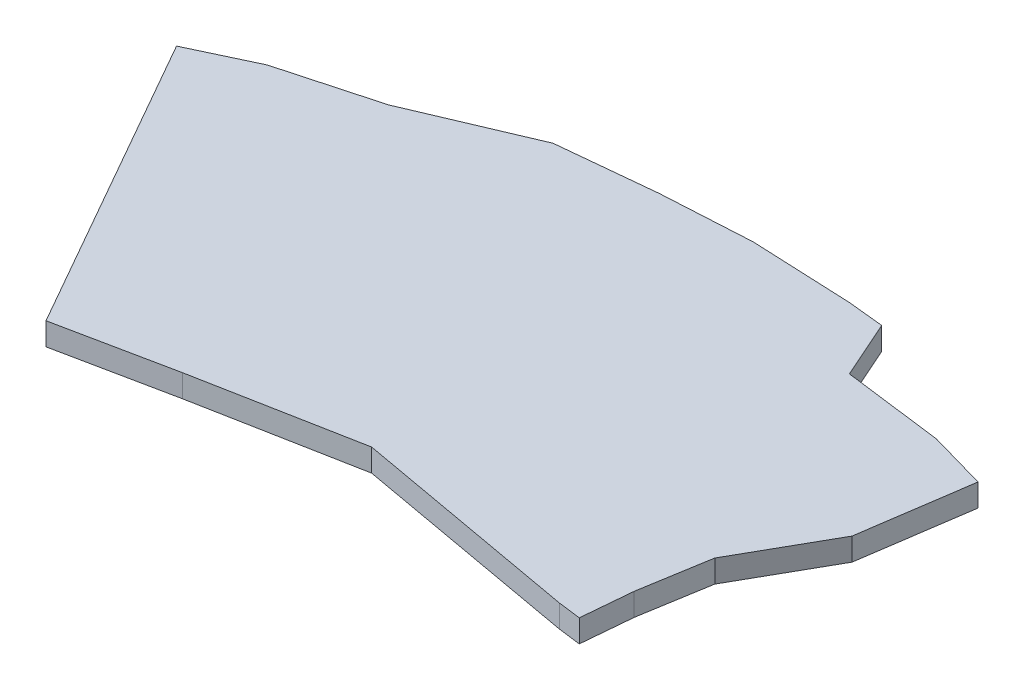
SolidWorks part; units mm, degrees
ref_plane "Спереди" through (0, 0, 0) normal (0, 0, 1) x (1, 0, 0)
ref_plane "Сверху" through (0, 0, 0) normal (0, 1, 0) x (1, 0, 0)
ref_plane "Справа" through (0, 0, 0) normal (1, 0, 0) x (0, 0, -1)
sketch "Sketch1" plane through (0, 0, 0) normal (0, 1, 0) x (1, 0, 0)
  line L0 (-16.2561, 26.609) -> (-10.7964, 29.1722)
  line L4 (-2.3748, 31.4791) -> (7.8402, 35.8163)
  line L8 (16.3824, 36.6681) -> (24.2468, 37.1155)
  line L9 (24.2468, 37.1155) -> (33.2149, 36.7207)
  line L10 (33.2149, 36.7207) -> (36.3351, 36.3935)
  line L11 (36.3351, 36.3935) -> (38.6188, 31.2568)
  line L12 (38.6188, 31.2568) -> (47.4466, 30.1245)
  line L13 (47.4466, 30.1245) -> (52.5867, 28.6628)
  line L14 (52.5867, 28.6628) -> (51.1594, 18.9539)
  line L15 (51.1594, 18.9539) -> (46.7682, 11.1964)
  line L17 (43.3617, 0.8762) -> (23.0896, 4.5213)
  line L18 (23.0896, 4.5213) -> (9.0371, 1.8532)
  line L19 (9.0371, 1.8532) -> (-0.9868, -0.2064)
  line L20 (-0.9868, -0.2064) -> (-16.2561, 26.609)
  line L21 (-10.646, 26.029) -> (-1.0258, 28.7587)
  line L22 (-1.0258, 28.7587) -> (5.2095, 6.7841)
  line L23 (5.2095, 6.7841) -> (-3.5518, 4.2981)
  line L24 (-10.646, 26.029) -> (-5.4017, 7.5469)
  line L25 (7.8554, 33.1374) -> (17.7581, 34.5287)
  line L26 (17.7581, 34.5287) -> (20.9389, 11.8895)
  line L27 (20.9389, 11.8895) -> (11.0362, 10.4981)
  line L28 (11.0362, 10.4981) -> (7.8554, 33.1374)
  line L29 (24.1721, 34.8404) -> (23.1574, 12.3233)
  line L30 (23.1574, 12.3233) -> (33.1473, 11.8731)
  line L31 (33.1473, 11.8731) -> (34.162, 34.3903)
  line L32 (34.162, 34.3903) -> (24.1721, 34.8404)
  line L33 (38.3251, 28.9823) -> (48.1751, 27.2566)
  line L34 (48.1751, 27.2566) -> (44.2664, 4.9462)
  line L35 (44.2664, 4.9462) -> (34.4164, 6.6718)
  line L36 (34.4164, 6.6718) -> (38.3251, 28.9823)
  line L37 (-10.7964, 29.1722) -> (-2.3748, 31.4791)
  line L38 (7.8402, 35.8163) -> (16.3824, 36.6681)
  line L39 (46.7682, 11.1964) -> (45.7548, 5.0853)
  line L40 (45.7548, 5.0853) -> (45.3569, 0.6201)
  line L41 (45.3569, 0.6201) -> (43.3617, 0.8762)
  line L42 (11.3111, 44.4789) -> (16.3337, 8.7301) construction
  line L43 (-8.7492, 37.6606) -> (1.2172, 2.5372) construction
  line L44 (29.2007, 35.3626) -> (28.0257, 9.2891) construction
  line L45 (43.3853, 28.8911) -> (38.8105, 2.7788) construction
  dimension "D1" = 5
  dimension "D2" = 5
  dimension "D3" = 5
  dimension "D4" = 5
  dimension "D5" = 5
  dimension "D6" = 5
  dimension "D7" = 5
  dimension "D8" = 5
extrude "Boss-Extrude1" add sketch "Sketch1" along normal blind 0.1 contours L21 L24 L20 L23 L22 region at (-2.7059, 0, -16.4859)
extrude "Boss-Extrude2" add sketch "Sketch1<4>" against normal blind 0.4 separate body contours L28 L27 L26 L25 region at (14.3972, 0, -22.5134)
sketch "Sketch1<4>" plane through (0, 0, 0) normal (0, 1, 0) x (1, 0, 0) same geometry as "Sketch1"
extrude "Boss-Extrude3" add sketch "Sketch1<6>" against normal blind 1.6 separate body contours L31 L32 L29 L30 region at (28.6597, 0, -23.3568)
sketch "Sketch1<6>" plane through (0, 0, 0) normal (0, 1, 0) x (1, 0, 0) same geometry as "Sketch1"
extrude "Boss-Extrude4" add sketch "Sketch1<7>" against normal blind 1 separate body contours L36 L35 L34 L33 region at (41.2957, 0, -16.9642)
sketch "Sketch1<7>" plane through (0, 0, 0) normal (0, 1, 0) x (1, 0, 0) same geometry as "Sketch1"
extrude "Boss-Extrude6" add sketch "Sketch1<9>" along normal blind 2 contours L38 L4 L37 L0 L20 L24 L21 L22 L23 L19 L18 L17 L15 L14 L13 L12 L11 L10 L9 L8 L32 L31 L30 L29 L27 L28 L25 L26 L35 L36 L33 L34 | L21 L24 L20 L23 L22 | L28 L27 L26 L25 | L31 L32 L29 L30 | L36 L35 L34 L33 region at (-13.1934, 0, -27.1818) region at (-2.7059, 0, -16.4859) region at (14.3972, 0, -22.5134) region at (28.6597, 0, -23.3568) region at (41.2957, 0, -16.9642)
sketch "Sketch1<9>" plane through (0, 0, 0) normal (0, 1, 0) x (1, 0, 0) same geometry as "Sketch1"
extrude "Cut-Extrude1" cut sketch "Sketch1<11>" along normal blind 0.1 contours L21 L24 L20 L23 L22 region at (-2.7059, 0, -16.4859)
sketch "Sketch1<11>" plane through (0, 0, 0) normal (0, 1, 0) x (1, 0, 0) same geometry as "Sketch1"
